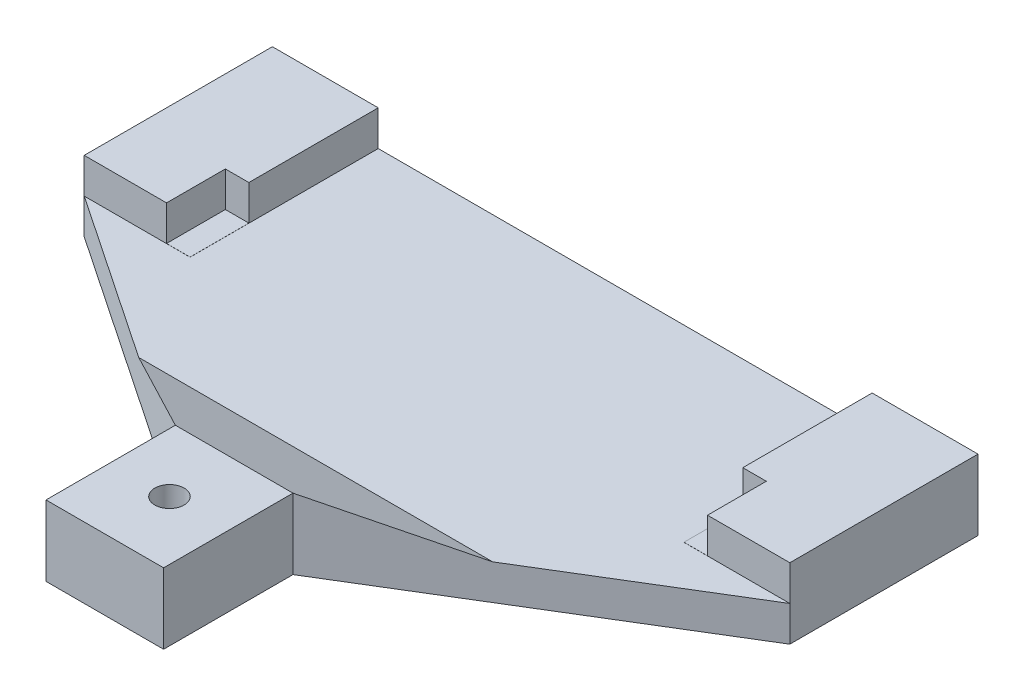
SolidWorks part; units mm, degrees
ref_plane "Plan de face" through (0, 0, 0) normal (0, 0, 1) x (1, 0, 0)
ref_plane "Plan de dessus" through (0, 0, 0) normal (0, 1, 0) x (1, 0, 0)
ref_plane "Plan de droite" through (0, 0, 0) normal (1, 0, 0) x (0, 0, -1)
sketch "Esquisse1" plane through (0, 0, 0) normal (0, 0, 1) x (1, 0, 0)
  line L1 (0, 0) -> (60, 0)
  line L2 (0, 0) -> (0, 6)
  line L3 (0, 6) -> (60, 6)
  line L4 (60, 0) -> (60, 6)
  dimension "D1" = 6
  dimension "D2" = 60
extrude "Boss.-Extru.1" add sketch "Esquisse1" along normal blind 60
sketch "Esquisse2" plane through (0, 0, 0) normal (0, 0, -1) x (-1, 0, 0)
  line L0 (-60, 6) -> (0, 6) construction
  line L1 (-60, 0) -> (-60, 6) construction
  line L2 (0, 6) -> (0, 0) construction
  circle A0 centre (-54, 3) radius 1.25
  circle A1 centre (-5.75, 3) radius 1.25
  dimension "D6" = 2.5
  dimension "D7" = 2.5
  dimension "D1" = 48.25
  dimension "D2" = 3
  dimension "D3" = 3
  dimension "D4" = 6
  dimension "D5" = 5.75
extrude "Enlèv. mat.-Extru.1" cut sketch "Esquisse2" against normal blind 10
sketch "Esquisse3" plane through (0, 6, 0) normal (0, 1, 0) x (1, 0, 0)
  line L0 (60, -60) -> (60, 0) construction
  line L1 (60, 0) -> (0, 0) construction
  circle A0 centre (28.75, -37.5) radius 1.25
  dimension "D1" = 2.5
  dimension "D2" = 31.25
  dimension "D3" = 37.5
extrude "Enlèv. mat.-Extru.2" cut sketch "Esquisse3" against normal blind 15
sketch "Esquisse4" plane through (0, 6, 0) normal (0, 1, 0) x (1, 0, 0)
  line L0 (0, -16) -> (9, -16)
  line L1 (0, -60) -> (0, 0) construction
  line L2 (9, -16) -> (9, 0)
  line L3 (60, 0) -> (0, 0) construction
  line L4 (9, 0) -> (51, 0)
  line L5 (51, 0) -> (51, -16)
  line L6 (51, -16) -> (60, -16)
  line L7 (60, -60) -> (60, 0) construction
  line L8 (60, -16) -> (60, -60)
  line L9 (60, -60) -> (0, -60)
  line L10 (0, -60) -> (0, -16)
  line L11 (23.75, -43) -> (33.75, -43)
  line L12 (33.75, -43) -> (33.75, -32)
  line L13 (33.75, -32) -> (23.75, -32)
  line L14 (23.75, -32) -> (23.75, -43)
  dimension "D1" = 9
  dimension "D2" = 9
  dimension "D3" = 16
  dimension "D4" = 16
  dimension "D5" = 17
  dimension "D6" = 32
  dimension "D7" = 23.75
  dimension "D8" = 26.25
extrude "Enlèv. mat.-Extru.3" cut sketch "Esquisse4" against normal blind 3
sketch "Esquisse5" plane through (0, 3, 0) normal (0, 1, 0) x (1, 0, 0)
  line L0 (60, -16) -> (33.75, -32)
  line L1 (33.75, -32) -> (33.75, -43)
  line L2 (33.75, -43) -> (23.75, -43)
  line L3 (23.75, -43) -> (23.75, -32)
  line L4 (23.75, -32) -> (0, -16)
  line L5 (0, -16) -> (-21.5949, -85.4755)
  line L6 (-21.5949, -85.4755) -> (75.4145, -69.9308)
  line L7 (75.4145, -69.9308) -> (60, -16)
extrude "Enlèv. mat.-Extru.4" cut sketch "Esquisse5" against normal blind 52
chamfer "Chanfrein1" distance 3 angle 65 1 edges at (28.75, 3, 32) first distance on face at (28.75, 4.5, 32)
sketch "Esquisse6" plane through (0, 6, 0) normal (0, 1, 0) x (1, 0, 0)
  line L1 (51, -16) -> (53, -16)
  line L2 (51, -16) -> (51, -11)
  line L3 (51, -11) -> (53, -11)
  line L4 (53, -16) -> (53, -11)
  line L5 (9, -16) -> (7, -16)
  line L6 (9, -16) -> (9, -11)
  line L7 (9, -11) -> (7, -11)
  line L8 (7, -16) -> (7, -11)
  dimension "D1" = 2
  dimension "D2" = 2
  dimension "D3" = 5
  dimension "D4" = 5
extrude "Enlèv. mat.-Extru.16" cut sketch "Esquisse6" against normal blind 2.99
